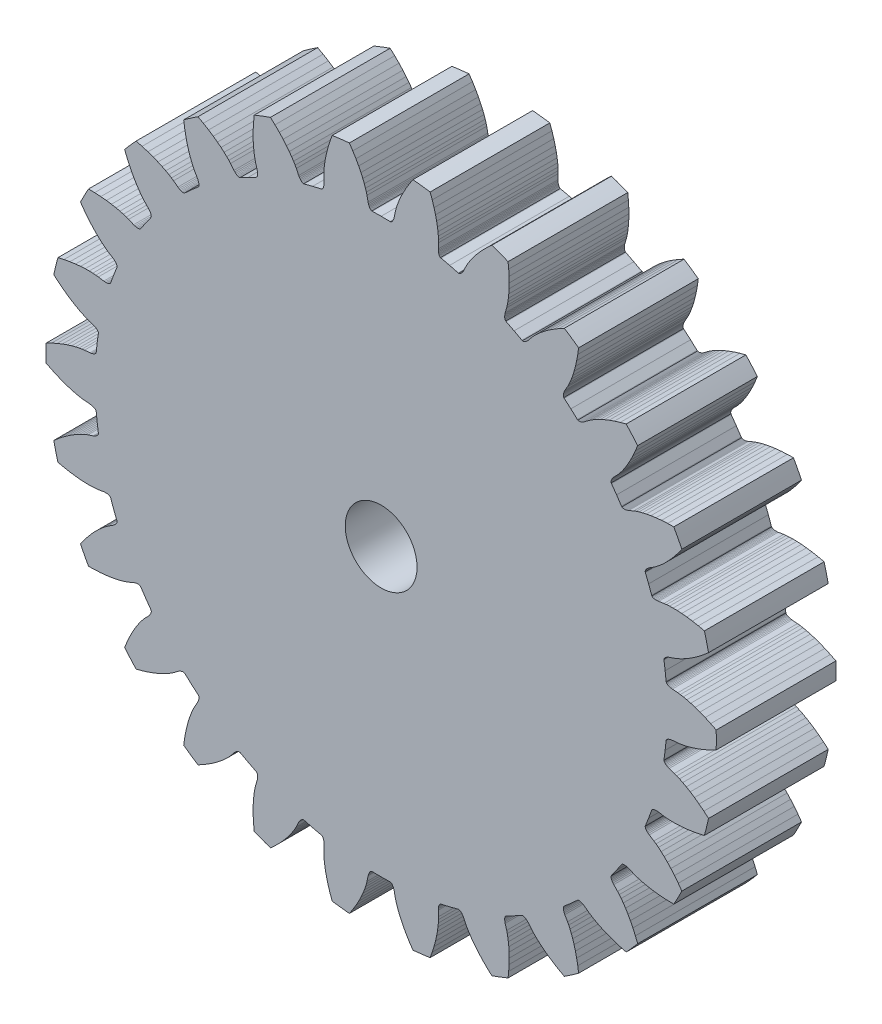
SolidWorks part; units mm, degrees
ref_plane "Front Plane" through (0, 0, 0) normal (0, 0, 1) x (1, 0, 0)
ref_plane "Top Plane" through (0, 0, 0) normal (0, 1, 0) x (1, 0, 0)
ref_plane "Right Plane" through (0, 0, 0) normal (1, 0, 0) x (0, 0, -1)
sketch "Model" plane through (0, 0, 0) normal (0, 0, 1) x (1, 0, 0)
  line L0 (13.4794, 2.8306) -> (13.2793, 2.6732)
  line L1 (13.2793, 2.6732) -> (13.0886, 2.5357)
  line L2 (13.0886, 2.5357) -> (12.9106, 2.4184)
  line L3 (12.9106, 2.4184) -> (12.7455, 2.3192)
  line L4 (12.7455, 2.3192) -> (12.5973, 2.2385)
  line L5 (12.5973, 2.2385) -> (12.4633, 2.1725)
  line L6 (12.4633, 2.1725) -> (12.3474, 2.1214)
  line L7 (12.3474, 2.1214) -> (12.2485, 2.0827)
  line L8 (12.2485, 2.0827) -> (12.0308, 2.0106)
  line L9 (12.0308, 2.0106) -> (11.9819, 1.9899)
  line L10 (11.9819, 1.9899) -> (11.9391, 1.9681)
  line L11 (11.9391, 1.9681) -> (11.9025, 1.9455)
  line L12 (11.9025, 1.9455) -> (11.8721, 1.9224)
  line L13 (11.8721, 1.9224) -> (11.8478, 1.899)
  line L14 (11.8478, 1.899) -> (11.8298, 1.8755)
  line L15 (11.8298, 1.8755) -> (11.8179, 1.8522)
  line L16 (11.8179, 1.8522) -> (11.8122, 1.8294)
  line L17 (11.8122, 1.8294) -> (11.8126, 1.8072)
  line L18 (11.8126, 1.8072) -> (11.8629, 1.4404)
  line L19 (11.8629, 1.4404) -> (11.9018, 1.0722)
  line L20 (11.9018, 1.0722) -> (11.9067, 1.0506)
  line L21 (11.9067, 1.0506) -> (11.9178, 1.0298)
  line L22 (11.9178, 1.0298) -> (11.9349, 1.0101)
  line L23 (11.9349, 1.0101) -> (11.958, 0.9916)
  line L24 (11.958, 0.9916) -> (11.9871, 0.9747)
  line L25 (11.9871, 0.9747) -> (12.0222, 0.9595)
  line L26 (12.0222, 0.9595) -> (12.0632, 0.9463)
  line L27 (12.0632, 0.9463) -> (12.1099, 0.9354)
  line L28 (12.1099, 0.9354) -> (12.1623, 0.927)
  line L29 (12.1623, 0.927) -> (12.391, 0.9091)
  line L30 (12.391, 0.9091) -> (12.4963, 0.8951)
  line L31 (12.4963, 0.8951) -> (12.6211, 0.8732)
  line L32 (12.6211, 0.8732) -> (12.7669, 0.8413)
  line L33 (12.7669, 0.8413) -> (12.9302, 0.7984)
  line L34 (12.9302, 0.7984) -> (13.1142, 0.7416)
  line L35 (13.1142, 0.7416) -> (13.3151, 0.6703)
  line L36 (13.3151, 0.6703) -> (13.5332, 0.5824)
  line L37 (13.5332, 0.5824) -> (13.7651, 0.4774)
  line L38 (13.7651, 0.4774) -> (13.9953, 0.3618)
  line L39 (13.9953, -0.3618) -> (13.7651, -0.4774)
  line L40 (13.7651, -0.4774) -> (13.5332, -0.5824)
  line L41 (13.5332, -0.5824) -> (13.3151, -0.6703)
  line L42 (13.3151, -0.6703) -> (13.1142, -0.7416)
  line L43 (13.1142, -0.7416) -> (12.9302, -0.7984)
  line L44 (12.9302, -0.7984) -> (12.7669, -0.8413)
  line L45 (12.7669, -0.8413) -> (12.6211, -0.8732)
  line L46 (12.6211, -0.8732) -> (12.4963, -0.8951)
  line L47 (12.4963, -0.8951) -> (12.391, -0.9091)
  line L48 (12.391, -0.9091) -> (12.1623, -0.927)
  line L49 (12.1623, -0.927) -> (12.1099, -0.9354)
  line L50 (12.1099, -0.9354) -> (12.0632, -0.9463)
  line L51 (12.0632, -0.9463) -> (12.0222, -0.9595)
  line L52 (12.0222, -0.9595) -> (11.9871, -0.9747)
  line L53 (11.9871, -0.9747) -> (11.958, -0.9916)
  line L54 (11.958, -0.9916) -> (11.9349, -1.0101)
  line L55 (11.9349, -1.0101) -> (11.9178, -1.0298)
  line L56 (11.9178, -1.0298) -> (11.9067, -1.0506)
  line L57 (11.9067, -1.0506) -> (11.9018, -1.0722)
  line L58 (11.9018, -1.0722) -> (11.8629, -1.4404)
  line L59 (11.8629, -1.4404) -> (11.8126, -1.8072)
  line L60 (11.8126, -1.8072) -> (11.8122, -1.8294)
  line L61 (11.8122, -1.8294) -> (11.8179, -1.8522)
  line L62 (11.8179, -1.8522) -> (11.8298, -1.8755)
  line L63 (11.8298, -1.8755) -> (11.8478, -1.899)
  line L64 (11.8478, -1.899) -> (11.8721, -1.9224)
  line L65 (11.8721, -1.9224) -> (11.9025, -1.9455)
  line L66 (11.9025, -1.9455) -> (11.9391, -1.9681)
  line L67 (11.9391, -1.9681) -> (11.9819, -1.9899)
  line L68 (11.9819, -1.9899) -> (12.0308, -2.0106)
  line L69 (12.0308, -2.0106) -> (12.2485, -2.0827)
  line L70 (12.2485, -2.0827) -> (12.3474, -2.1214)
  line L71 (12.3474, -2.1214) -> (12.4633, -2.1725)
  line L72 (12.4633, -2.1725) -> (12.5973, -2.2385)
  line L73 (12.5973, -2.2385) -> (12.7455, -2.3192)
  line L74 (12.7455, -2.3192) -> (12.9106, -2.4184)
  line L75 (12.9106, -2.4184) -> (13.0886, -2.5357)
  line L76 (13.0886, -2.5357) -> (13.2793, -2.6732)
  line L77 (13.2793, -2.6732) -> (13.4794, -2.8306)
  line L78 (13.4794, -2.8306) -> (13.6752, -2.9981)
  line L79 (13.5021, -3.7006) -> (13.2509, -3.7578)
  line L80 (13.2509, -3.7578) -> (13.0005, -3.8042)
  line L81 (13.0005, -3.8042) -> (12.7678, -3.8373)
  line L82 (12.7678, -3.8373) -> (12.5557, -3.8585)
  line L83 (12.5557, -3.8585) -> (12.3634, -3.8696)
  line L84 (12.3634, -3.8696) -> (12.1946, -3.8722)
  line L85 (12.1946, -3.8722) -> (12.0453, -3.8683)
  line L86 (12.0453, -3.8683) -> (11.919, -3.8597)
  line L87 (11.919, -3.8597) -> (11.8134, -3.848)
  line L88 (11.8134, -3.848) -> (11.5871, -3.8107)
  line L89 (11.5871, -3.8107) -> (11.5341, -3.8063)
  line L90 (11.5341, -3.8063) -> (11.4862, -3.8057)
  line L91 (11.4862, -3.8057) -> (11.4433, -3.8087)
  line L92 (11.4433, -3.8087) -> (11.4056, -3.815)
  line L93 (11.4056, -3.815) -> (11.3732, -3.8245)
  line L94 (11.3732, -3.8245) -> (11.3463, -3.8369)
  line L95 (11.3463, -3.8369) -> (11.325, -3.852)
  line L96 (11.325, -3.852) -> (11.3093, -3.8696)
  line L97 (11.3093, -3.8696) -> (11.2994, -3.8894)
  line L98 (11.2994, -3.8894) -> (11.1734, -4.2375)
  line L99 (11.1734, -4.2375) -> (11.0368, -4.5816)
  line L100 (11.0368, -4.5816) -> (11.0311, -4.603)
  line L101 (11.0311, -4.603) -> (11.0312, -4.6266)
  line L102 (11.0312, -4.6266) -> (11.0372, -4.652)
  line L103 (11.0372, -4.652) -> (11.0491, -4.6791)
  line L104 (11.0491, -4.6791) -> (11.067, -4.7077)
  line L105 (11.067, -4.7077) -> (11.091, -4.7374)
  line L106 (11.091, -4.7374) -> (11.1212, -4.7681)
  line L107 (11.1212, -4.7681) -> (11.1575, -4.7995)
  line L108 (11.1575, -4.7995) -> (11.2, -4.8313)
  line L109 (11.2, -4.8313) -> (11.3942, -4.9534)
  line L110 (11.3942, -4.9534) -> (11.4809, -5.0147)
  line L111 (11.4809, -5.0147) -> (11.5812, -5.0921)
  line L112 (11.5812, -5.0921) -> (11.6955, -5.1881)
  line L113 (11.6955, -5.1881) -> (11.8201, -5.302)
  line L114 (11.8201, -5.302) -> (11.9567, -5.4378)
  line L115 (11.9567, -5.4378) -> (12.1014, -5.5943)
  line L116 (12.1014, -5.5943) -> (12.2537, -5.7735)
  line L117 (12.2537, -5.7735) -> (12.4103, -5.9742)
  line L118 (12.4103, -5.9742) -> (12.5604, -6.1836)
  line L119 (12.2241, -6.8243) -> (11.9665, -6.8197)
  line L120 (11.9665, -6.8197) -> (11.7124, -6.8049)
  line L121 (11.7124, -6.8049) -> (11.4784, -6.7813)
  line L122 (11.4784, -6.7813) -> (11.2674, -6.7511)
  line L123 (11.2674, -6.7511) -> (11.0781, -6.7159)
  line L124 (11.0781, -6.7159) -> (10.9136, -6.678)
  line L125 (10.9136, -6.678) -> (10.7696, -6.6385)
  line L126 (10.7696, -6.6385) -> (10.6489, -6.5999)
  line L127 (10.6489, -6.5999) -> (10.5492, -6.5634)
  line L128 (10.5492, -6.5634) -> (10.3384, -6.4729)
  line L129 (10.3384, -6.4729) -> (10.2881, -6.456)
  line L130 (10.2881, -6.456) -> (10.2416, -6.444)
  line L131 (10.2416, -6.444) -> (10.1993, -6.4366)
  line L132 (10.1993, -6.4366) -> (10.1611, -6.4337)
  line L133 (10.1611, -6.4337) -> (10.1275, -6.4352)
  line L134 (10.1275, -6.4352) -> (10.0984, -6.4408)
  line L135 (10.0984, -6.4408) -> (10.0741, -6.4503)
  line L136 (10.0741, -6.4503) -> (10.0546, -6.4636)
  line L137 (10.0546, -6.4636) -> (10.0402, -6.4805)
  line L138 (10.0402, -6.4805) -> (9.8347, -6.7884)
  line L139 (9.8347, -6.7884) -> (9.6197, -7.0898)
  line L140 (9.6197, -7.0898) -> (9.609, -7.1092)
  line L141 (9.609, -7.1092) -> (9.6035, -7.1321)
  line L142 (9.6035, -7.1321) -> (9.6032, -7.1582)
  line L143 (9.6032, -7.1582) -> (9.6083, -7.1874)
  line L144 (9.6083, -7.1874) -> (9.6188, -7.2194)
  line L145 (9.6188, -7.2194) -> (9.635, -7.254)
  line L146 (9.635, -7.254) -> (9.6569, -7.291)
  line L147 (9.6569, -7.291) -> (9.6847, -7.3302)
  line L148 (9.6847, -7.3302) -> (9.7184, -7.3713)
  line L149 (9.7184, -7.3713) -> (9.8777, -7.5363)
  line L150 (9.8777, -7.5363) -> (9.9472, -7.6166)
  line L151 (9.9472, -7.6166) -> (10.0261, -7.7157)
  line L152 (10.0261, -7.7157) -> (10.1141, -7.8363)
  line L153 (10.1141, -7.8363) -> (10.2078, -7.9767)
  line L154 (10.2078, -7.9767) -> (10.3079, -8.1412)
  line L155 (10.3079, -8.1412) -> (10.411, -8.3278)
  line L156 (10.411, -8.3278) -> (10.5159, -8.5382)
  line L157 (10.5159, -8.5382) -> (10.6199, -8.7706)
  line L158 (10.6199, -8.7706) -> (10.7155, -9.0098)
  line L159 (10.2357, -9.5514) -> (9.9867, -9.4853)
  line L160 (9.9867, -9.4853) -> (9.7435, -9.4101)
  line L161 (9.7435, -9.4101) -> (9.522, -9.3312)
  line L162 (9.522, -9.3312) -> (9.3244, -9.2514)
  line L163 (9.3244, -9.2514) -> (9.149, -9.1719)
  line L164 (9.149, -9.1719) -> (8.9983, -9.0958)
  line L165 (8.9983, -9.0958) -> (8.8679, -9.0229)
  line L166 (8.8679, -9.0229) -> (8.76, -8.9566)
  line L167 (8.76, -8.9566) -> (8.672, -8.8972)
  line L168 (8.672, -8.8972) -> (8.4889, -8.759)
  line L169 (8.4889, -8.759) -> (8.4441, -8.7305)
  line L170 (8.4441, -8.7305) -> (8.4019, -8.7077)
  line L171 (8.4019, -8.7077) -> (8.3625, -8.6904)
  line L172 (8.3625, -8.6904) -> (8.3262, -8.6785)
  line L173 (8.3262, -8.6785) -> (8.2931, -8.6719)
  line L174 (8.2931, -8.6719) -> (8.2636, -8.6703)
  line L175 (8.2636, -8.6703) -> (8.2377, -8.6738)
  line L176 (8.2377, -8.6738) -> (8.2156, -8.682)
  line L177 (8.2156, -8.682) -> (8.1976, -8.6949)
  line L178 (8.1976, -8.6949) -> (7.9243, -8.9447)
  line L179 (7.9243, -8.9447) -> (7.6434, -9.1859)
  line L180 (7.6434, -9.1859) -> (7.6284, -9.2022)
  line L181 (7.6284, -9.2022) -> (7.6176, -9.2231)
  line L182 (7.6176, -9.2231) -> (7.6111, -9.2484)
  line L183 (7.6111, -9.2484) -> (7.609, -9.278)
  line L184 (7.609, -9.278) -> (7.6116, -9.3116)
  line L185 (7.6116, -9.3116) -> (7.619, -9.349)
  line L186 (7.619, -9.349) -> (7.6315, -9.3902)
  line L187 (7.6315, -9.3902) -> (7.649, -9.4349)
  line L188 (7.649, -9.4349) -> (7.6719, -9.4828)
  line L189 (7.6719, -9.4828) -> (7.7871, -9.6812)
  line L190 (7.7871, -9.6812) -> (7.8354, -9.7758)
  line L191 (7.8354, -9.7758) -> (7.8883, -9.8909)
  line L192 (7.8883, -9.8909) -> (7.9448, -10.0291)
  line L193 (7.9448, -10.0291) -> (8.0022, -10.1878)
  line L194 (8.0022, -10.1878) -> (8.06, -10.3715)
  line L195 (8.06, -10.3715) -> (8.1155, -10.5773)
  line L196 (8.1155, -10.5773) -> (8.167, -10.8067)
  line L197 (8.167, -10.8067) -> (8.2124, -11.0572)
  line L198 (8.2124, -11.0572) -> (8.248, -11.3124)
  line L199 (7.6525, -11.7234) -> (7.4265, -11.5997)
  line L200 (7.4265, -11.5997) -> (7.2084, -11.4684)
  line L201 (7.2084, -11.4684) -> (7.0122, -11.3389)
  line L202 (7.0122, -11.3389) -> (6.8394, -11.2141)
  line L203 (6.8394, -11.2141) -> (6.6881, -11.0948)
  line L204 (6.6881, -11.0948) -> (6.5601, -10.9849)
  line L205 (6.5601, -10.9849) -> (6.4509, -10.883)
  line L206 (6.4509, -10.883) -> (6.362, -10.7928)
  line L207 (6.362, -10.7928) -> (6.2907, -10.714)
  line L208 (6.2907, -10.714) -> (6.1461, -10.536)
  line L209 (6.1461, -10.536) -> (6.1094, -10.4976)
  line L210 (6.1094, -10.4976) -> (6.0738, -10.4654)
  line L211 (6.0738, -10.4654) -> (6.0398, -10.4391)
  line L212 (6.0398, -10.4391) -> (6.0073, -10.4189)
  line L213 (6.0073, -10.4189) -> (5.9769, -10.4045)
  line L214 (5.9769, -10.4045) -> (5.9485, -10.396)
  line L215 (5.9485, -10.396) -> (5.9225, -10.3931)
  line L216 (5.9225, -10.3931) -> (5.8991, -10.3959)
  line L217 (5.8991, -10.3959) -> (5.8786, -10.4041)
  line L218 (5.8786, -10.4041) -> (5.5534, -10.5812)
  line L219 (5.5534, -10.5812) -> (5.223, -10.7482)
  line L220 (5.223, -10.7482) -> (5.2045, -10.7604)
  line L221 (5.2045, -10.7604) -> (5.189, -10.7781)
  line L222 (5.189, -10.7781) -> (5.1766, -10.8011)
  line L223 (5.1766, -10.8011) -> (5.1675, -10.8293)
  line L224 (5.1675, -10.8293) -> (5.162, -10.8626)
  line L225 (5.162, -10.8626) -> (5.1603, -10.9007)
  line L226 (5.1603, -10.9007) -> (5.1625, -10.9437)
  line L227 (5.1625, -10.9437) -> (5.1689, -10.9912)
  line L228 (5.1689, -10.9912) -> (5.1796, -11.0433)
  line L229 (5.1796, -11.0433) -> (5.2439, -11.2634)
  line L230 (5.2439, -11.2634) -> (5.2682, -11.3668)
  line L231 (5.2682, -11.3668) -> (5.292, -11.4912)
  line L232 (5.292, -11.4912) -> (5.3139, -11.639)
  line L233 (5.3139, -11.639) -> (5.3316, -11.8068)
  line L234 (5.3316, -11.8068) -> (5.3438, -11.999)
  line L235 (5.3438, -11.999) -> (5.3483, -12.2121)
  line L236 (5.3483, -12.2121) -> (5.3435, -12.4472)
  line L237 (5.3435, -12.4472) -> (5.3276, -12.7013)
  line L238 (5.3276, -12.7013) -> (5.3011, -12.9576)
  line L239 (4.6246, -13.2141) -> (4.4348, -13.0399)
  line L240 (4.4348, -13.0399) -> (4.2544, -12.8603)
  line L241 (4.2544, -12.8603) -> (4.0949, -12.6875)
  line L242 (4.0949, -12.6875) -> (3.957, -12.525)
  line L243 (3.957, -12.525) -> (3.8386, -12.373)
  line L244 (3.8386, -12.373) -> (3.7406, -12.2356)
  line L245 (3.7406, -12.2356) -> (3.659, -12.1106)
  line L246 (3.659, -12.1106) -> (3.5943, -12.0017)
  line L247 (3.5943, -12.0017) -> (3.5439, -11.9082)
  line L248 (3.5439, -11.9082) -> (3.4461, -11.7007)
  line L249 (3.4461, -11.7007) -> (3.4196, -11.6546)
  line L250 (3.4196, -11.6546) -> (3.3928, -11.6148)
  line L251 (3.3928, -11.6148) -> (3.366, -11.5812)
  line L252 (3.366, -11.5812) -> (3.3394, -11.5538)
  line L253 (3.3394, -11.5538) -> (3.3132, -11.5326)
  line L254 (3.3132, -11.5326) -> (3.2877, -11.5175)
  line L255 (3.2877, -11.5175) -> (3.2632, -11.5085)
  line L256 (3.2632, -11.5085) -> (3.2398, -11.5055)
  line L257 (3.2398, -11.5055) -> (3.2179, -11.5086)
  line L258 (3.2179, -11.5086) -> (2.8598, -11.6028)
  line L259 (2.8598, -11.6028) -> (2.499, -11.6858)
  line L260 (2.499, -11.6858) -> (2.4782, -11.6933)
  line L261 (2.4782, -11.6933) -> (2.4589, -11.7067)
  line L262 (2.4589, -11.7067) -> (2.4413, -11.7261)
  line L263 (2.4413, -11.7261) -> (2.4257, -11.7513)
  line L264 (2.4257, -11.7513) -> (2.4124, -11.7823)
  line L265 (2.4124, -11.7823) -> (2.4016, -11.8189)
  line L266 (2.4016, -11.8189) -> (2.3935, -11.8611)
  line L267 (2.3935, -11.8611) -> (2.3883, -11.9088)
  line L268 (2.3883, -11.9088) -> (2.3862, -11.9619)
  line L269 (2.3862, -11.9619) -> (2.396, -12.1911)
  line L270 (2.396, -12.1911) -> (2.3949, -12.2973)
  line L271 (2.3949, -12.2973) -> (2.3882, -12.4238)
  line L272 (2.3882, -12.4238) -> (2.3741, -12.5724)
  line L273 (2.3741, -12.5724) -> (2.3511, -12.7397)
  line L274 (2.3511, -12.7397) -> (2.3169, -12.9292)
  line L275 (2.3169, -12.9292) -> (2.2704, -13.1372)
  line L276 (2.2704, -13.1372) -> (2.2094, -13.3643)
  line L277 (2.2094, -13.3643) -> (2.1332, -13.6072)
  line L278 (2.1332, -13.6072) -> (2.0461, -13.8497)
  line L279 (1.3278, -13.9369) -> (1.1852, -13.7223)
  line L280 (1.1852, -13.7223) -> (1.0531, -13.5047)
  line L281 (1.0531, -13.5047) -> (0.9396, -13.2988)
  line L282 (0.9396, -13.2988) -> (0.8446, -13.108)
  line L283 (0.8446, -13.108) -> (0.766, -12.9321)
  line L284 (0.766, -12.9321) -> (0.7037, -12.7753)
  line L285 (0.7037, -12.7753) -> (0.6544, -12.6343)
  line L286 (0.6544, -12.6343) -> (0.6177, -12.5131)
  line L287 (0.6177, -12.5131) -> (0.5911, -12.4102)
  line L288 (0.5911, -12.4102) -> (0.5458, -12.1854)
  line L289 (0.5458, -12.1854) -> (0.5311, -12.1343)
  line L290 (0.5311, -12.1343) -> (0.5146, -12.0893)
  line L291 (0.5146, -12.0893) -> (0.4966, -12.0502)
  line L292 (0.4966, -12.0502) -> (0.4773, -12.0172)
  line L293 (0.4773, -12.0172) -> (0.457, -11.9904)
  line L294 (0.457, -11.9904) -> (0.4359, -11.9696)
  line L295 (0.4359, -11.9696) -> (0.4142, -11.955)
  line L296 (0.4142, -11.955) -> (0.3922, -11.9466)
  line L297 (0.3922, -11.9466) -> (0.3702, -11.9443)
  line L298 (0.3702, -11.9443) -> (0, -11.95)
  line L299 (0, -11.95) -> (-0.3702, -11.9443)
  line L300 (-0.3702, -11.9443) -> (-0.3922, -11.9466)
  line L301 (-0.3922, -11.9466) -> (-0.4142, -11.955)
  line L302 (-0.4142, -11.955) -> (-0.4359, -11.9696)
  line L303 (-0.4359, -11.9696) -> (-0.457, -11.9904)
  line L304 (-0.457, -11.9904) -> (-0.4773, -12.0172)
  line L305 (-0.4773, -12.0172) -> (-0.4966, -12.0502)
  line L306 (-0.4966, -12.0502) -> (-0.5146, -12.0893)
  line L307 (-0.5146, -12.0893) -> (-0.5311, -12.1343)
  line L308 (-0.5311, -12.1343) -> (-0.5458, -12.1854)
  line L309 (-0.5458, -12.1854) -> (-0.5911, -12.4102)
  line L310 (-0.5911, -12.4102) -> (-0.6177, -12.5131)
  line L311 (-0.6177, -12.5131) -> (-0.6544, -12.6343)
  line L312 (-0.6544, -12.6343) -> (-0.7037, -12.7753)
  line L313 (-0.7037, -12.7753) -> (-0.766, -12.9321)
  line L314 (-0.766, -12.9321) -> (-0.8446, -13.108)
  line L315 (-0.8446, -13.108) -> (-0.9396, -13.2988)
  line L316 (-0.9396, -13.2988) -> (-1.0531, -13.5047)
  line L317 (-1.0531, -13.5047) -> (-1.1852, -13.7223)
  line L318 (-1.1852, -13.7223) -> (-1.3278, -13.9369)
  line L319 (-2.0461, -13.8497) -> (-2.1332, -13.6072)
  line L320 (-2.1332, -13.6072) -> (-2.2094, -13.3643)
  line L321 (-2.2094, -13.3643) -> (-2.2704, -13.1372)
  line L322 (-2.2704, -13.1372) -> (-2.3169, -12.9292)
  line L323 (-2.3169, -12.9292) -> (-2.3511, -12.7397)
  line L324 (-2.3511, -12.7397) -> (-2.3741, -12.5724)
  line L325 (-2.3741, -12.5724) -> (-2.3882, -12.4238)
  line L326 (-2.3882, -12.4238) -> (-2.3949, -12.2973)
  line L327 (-2.3949, -12.2973) -> (-2.396, -12.1911)
  line L328 (-2.396, -12.1911) -> (-2.3862, -11.9619)
  line L329 (-2.3862, -11.9619) -> (-2.3883, -11.9088)
  line L330 (-2.3883, -11.9088) -> (-2.3935, -11.8611)
  line L331 (-2.3935, -11.8611) -> (-2.4016, -11.8189)
  line L332 (-2.4016, -11.8189) -> (-2.4124, -11.7823)
  line L333 (-2.4124, -11.7823) -> (-2.4257, -11.7513)
  line L334 (-2.4257, -11.7513) -> (-2.4413, -11.7261)
  line L335 (-2.4413, -11.7261) -> (-2.4589, -11.7067)
  line L336 (-2.4589, -11.7067) -> (-2.4782, -11.6933)
  line L337 (-2.4782, -11.6933) -> (-2.499, -11.6858)
  line L338 (-2.499, -11.6858) -> (-2.8598, -11.6028)
  line L339 (-2.8598, -11.6028) -> (-3.2179, -11.5086)
  line L340 (-3.2179, -11.5086) -> (-3.2398, -11.5055)
  line L341 (-3.2398, -11.5055) -> (-3.2632, -11.5085)
  line L342 (-3.2632, -11.5085) -> (-3.2877, -11.5175)
  line L343 (-3.2877, -11.5175) -> (-3.3132, -11.5326)
  line L344 (-3.3132, -11.5326) -> (-3.3394, -11.5538)
  line L345 (-3.3394, -11.5538) -> (-3.366, -11.5812)
  line L346 (-3.366, -11.5812) -> (-3.3928, -11.6148)
  line L347 (-3.3928, -11.6148) -> (-3.4196, -11.6546)
  line L348 (-3.4196, -11.6546) -> (-3.4461, -11.7007)
  line L349 (-3.4461, -11.7007) -> (-3.5439, -11.9082)
  line L350 (-3.5439, -11.9082) -> (-3.5943, -12.0017)
  line L351 (-3.5943, -12.0017) -> (-3.659, -12.1106)
  line L352 (-3.659, -12.1106) -> (-3.7406, -12.2356)
  line L353 (-3.7406, -12.2356) -> (-3.8386, -12.373)
  line L354 (-3.8386, -12.373) -> (-3.957, -12.525)
  line L355 (-3.957, -12.525) -> (-4.0949, -12.6875)
  line L356 (-4.0949, -12.6875) -> (-4.2544, -12.8603)
  line L357 (-4.2544, -12.8603) -> (-4.4348, -13.0399)
  line L358 (-4.4348, -13.0399) -> (-4.6246, -13.2141)
  line L359 (-5.3011, -12.9576) -> (-5.3276, -12.7013)
  line L360 (-5.3276, -12.7013) -> (-5.3435, -12.4472)
  line L361 (-5.3435, -12.4472) -> (-5.3483, -12.2121)
  line L362 (-5.3483, -12.2121) -> (-5.3438, -11.999)
  line L363 (-5.3438, -11.999) -> (-5.3316, -11.8068)
  line L364 (-5.3316, -11.8068) -> (-5.3139, -11.639)
  line L365 (-5.3139, -11.639) -> (-5.292, -11.4912)
  line L366 (-5.292, -11.4912) -> (-5.2682, -11.3668)
  line L367 (-5.2682, -11.3668) -> (-5.2439, -11.2634)
  line L368 (-5.2439, -11.2634) -> (-5.1796, -11.0433)
  line L369 (-5.1796, -11.0433) -> (-5.1689, -10.9912)
  line L370 (-5.1689, -10.9912) -> (-5.1625, -10.9437)
  line L371 (-5.1625, -10.9437) -> (-5.1603, -10.9007)
  line L372 (-5.1603, -10.9007) -> (-5.162, -10.8626)
  line L373 (-5.162, -10.8626) -> (-5.1675, -10.8293)
  line L374 (-5.1675, -10.8293) -> (-5.1766, -10.8011)
  line L375 (-5.1766, -10.8011) -> (-5.189, -10.7781)
  line L376 (-5.189, -10.7781) -> (-5.2045, -10.7604)
  line L377 (-5.2045, -10.7604) -> (-5.223, -10.7482)
  line L378 (-5.223, -10.7482) -> (-5.5534, -10.5812)
  line L379 (-5.5534, -10.5812) -> (-5.8786, -10.4041)
  line L380 (-5.8786, -10.4041) -> (-5.8991, -10.3959)
  line L381 (-5.8991, -10.3959) -> (-5.9225, -10.3931)
  line L382 (-5.9225, -10.3931) -> (-5.9485, -10.396)
  line L383 (-5.9485, -10.396) -> (-5.9769, -10.4045)
  line L384 (-5.9769, -10.4045) -> (-6.0073, -10.4189)
  line L385 (-6.0073, -10.4189) -> (-6.0398, -10.4391)
  line L386 (-6.0398, -10.4391) -> (-6.0738, -10.4654)
  line L387 (-6.0738, -10.4654) -> (-6.1094, -10.4976)
  line L388 (-6.1094, -10.4976) -> (-6.1461, -10.536)
  line L389 (-6.1461, -10.536) -> (-6.2907, -10.714)
  line L390 (-6.2907, -10.714) -> (-6.362, -10.7928)
  line L391 (-6.362, -10.7928) -> (-6.4509, -10.883)
  line L392 (-6.4509, -10.883) -> (-6.5601, -10.9849)
  line L393 (-6.5601, -10.9849) -> (-6.6881, -11.0948)
  line L394 (-6.6881, -11.0948) -> (-6.8394, -11.2141)
  line L395 (-6.8394, -11.2141) -> (-7.0122, -11.3389)
  line L396 (-7.0122, -11.3389) -> (-7.2084, -11.4684)
  line L397 (-7.2084, -11.4684) -> (-7.4265, -11.5997)
  line L398 (-7.4265, -11.5997) -> (-7.6525, -11.7234)
  line L399 (-8.248, -11.3124) -> (-8.2124, -11.0572)
  line L400 (-8.2124, -11.0572) -> (-8.167, -10.8067)
  line L401 (-8.167, -10.8067) -> (-8.1155, -10.5773)
  line L402 (-8.1155, -10.5773) -> (-8.06, -10.3715)
  line L403 (-8.06, -10.3715) -> (-8.0022, -10.1878)
  line L404 (-8.0022, -10.1878) -> (-7.9448, -10.0291)
  line L405 (-7.9448, -10.0291) -> (-7.8883, -9.8909)
  line L406 (-7.8883, -9.8909) -> (-7.8354, -9.7758)
  line L407 (-7.8354, -9.7758) -> (-7.7871, -9.6812)
  line L408 (-7.7871, -9.6812) -> (-7.6719, -9.4828)
  line L409 (-7.6719, -9.4828) -> (-7.649, -9.4349)
  line L410 (-7.649, -9.4349) -> (-7.6315, -9.3902)
  line L411 (-7.6315, -9.3902) -> (-7.619, -9.349)
  line L412 (-7.619, -9.349) -> (-7.6116, -9.3116)
  line L413 (-7.6116, -9.3116) -> (-7.609, -9.278)
  line L414 (-7.609, -9.278) -> (-7.6111, -9.2484)
  line L415 (-7.6111, -9.2484) -> (-7.6176, -9.2231)
  line L416 (-7.6176, -9.2231) -> (-7.6284, -9.2022)
  line L417 (-7.6284, -9.2022) -> (-7.6434, -9.1859)
  line L418 (-7.6434, -9.1859) -> (-7.9243, -8.9447)
  line L419 (-7.9243, -8.9447) -> (-8.1976, -8.6949)
  line L420 (-8.1976, -8.6949) -> (-8.2156, -8.682)
  line L421 (-8.2156, -8.682) -> (-8.2377, -8.6738)
  line L422 (-8.2377, -8.6738) -> (-8.2636, -8.6703)
  line L423 (-8.2636, -8.6703) -> (-8.2931, -8.6719)
  line L424 (-8.2931, -8.6719) -> (-8.3262, -8.6785)
  line L425 (-8.3262, -8.6785) -> (-8.3625, -8.6904)
  line L426 (-8.3625, -8.6904) -> (-8.4019, -8.7077)
  line L427 (-8.4019, -8.7077) -> (-8.4441, -8.7305)
  line L428 (-8.4441, -8.7305) -> (-8.4889, -8.759)
  line L429 (-8.4889, -8.759) -> (-8.672, -8.8972)
  line L430 (-8.672, -8.8972) -> (-8.76, -8.9566)
  line L431 (-8.76, -8.9566) -> (-8.8679, -9.0229)
  line L432 (-8.8679, -9.0229) -> (-8.9983, -9.0958)
  line L433 (-8.9983, -9.0958) -> (-9.149, -9.1719)
  line L434 (-9.149, -9.1719) -> (-9.3244, -9.2514)
  line L435 (-9.3244, -9.2514) -> (-9.522, -9.3312)
  line L436 (-9.522, -9.3312) -> (-9.7435, -9.4101)
  line L437 (-9.7435, -9.4101) -> (-9.9867, -9.4853)
  line L438 (-9.9867, -9.4853) -> (-10.2358, -9.5514)
  line L439 (-10.7156, -9.0098) -> (-10.6199, -8.7706)
  line L440 (-10.6199, -8.7706) -> (-10.5159, -8.5382)
  line L441 (-10.5159, -8.5382) -> (-10.411, -8.3278)
  line L442 (-10.411, -8.3278) -> (-10.3079, -8.1412)
  line L443 (-10.3079, -8.1412) -> (-10.2078, -7.9767)
  line L444 (-10.2078, -7.9767) -> (-10.1141, -7.8363)
  line L445 (-10.1141, -7.8363) -> (-10.0261, -7.7157)
  line L446 (-10.0261, -7.7157) -> (-9.9472, -7.6166)
  line L447 (-9.9472, -7.6166) -> (-9.8777, -7.5363)
  line L448 (-9.8777, -7.5363) -> (-9.7184, -7.3713)
  line L449 (-9.7184, -7.3713) -> (-9.6847, -7.3302)
  line L450 (-9.6847, -7.3302) -> (-9.6569, -7.291)
  line L451 (-9.6569, -7.291) -> (-9.635, -7.254)
  line L452 (-9.635, -7.254) -> (-9.6188, -7.2194)
  line L453 (-9.6188, -7.2194) -> (-9.6083, -7.1874)
  line L454 (-9.6083, -7.1874) -> (-9.6032, -7.1582)
  line L455 (-9.6032, -7.1582) -> (-9.6035, -7.1321)
  line L456 (-9.6035, -7.1321) -> (-9.609, -7.1092)
  line L457 (-9.609, -7.1092) -> (-9.6197, -7.0898)
  line L458 (-9.6197, -7.0898) -> (-9.8347, -6.7884)
  line L459 (-9.8347, -6.7884) -> (-10.0402, -6.4805)
  line L460 (-10.0402, -6.4805) -> (-10.0546, -6.4636)
  line L461 (-10.0546, -6.4636) -> (-10.0741, -6.4503)
  line L462 (-10.0741, -6.4503) -> (-10.0984, -6.4408)
  line L463 (-10.0984, -6.4408) -> (-10.1275, -6.4352)
  line L464 (-10.1275, -6.4352) -> (-10.1611, -6.4337)
  line L465 (-10.1611, -6.4337) -> (-10.1993, -6.4366)
  line L466 (-10.1993, -6.4366) -> (-10.2416, -6.444)
  line L467 (-10.2416, -6.444) -> (-10.2881, -6.456)
  line L468 (-10.2881, -6.456) -> (-10.3384, -6.4729)
  line L469 (-10.3384, -6.4729) -> (-10.5492, -6.5634)
  line L470 (-10.5492, -6.5634) -> (-10.6489, -6.5999)
  line L471 (-10.6489, -6.5999) -> (-10.7696, -6.6385)
  line L472 (-10.7696, -6.6385) -> (-10.9136, -6.678)
  line L473 (-10.9136, -6.678) -> (-11.0781, -6.7159)
  line L474 (-11.0781, -6.7159) -> (-11.2674, -6.7511)
  line L475 (-11.2674, -6.7511) -> (-11.4784, -6.7813)
  line L476 (-11.4784, -6.7813) -> (-11.7124, -6.8049)
  line L477 (-11.7124, -6.8049) -> (-11.9665, -6.8197)
  line L478 (-11.9665, -6.8197) -> (-12.2241, -6.8243)
  line L479 (-12.5604, -6.1836) -> (-12.4103, -5.9742)
  line L480 (-12.4103, -5.9742) -> (-12.2537, -5.7735)
  line L481 (-12.2537, -5.7735) -> (-12.1014, -5.5943)
  line L482 (-12.1014, -5.5943) -> (-11.9567, -5.4378)
  line L483 (-11.9567, -5.4378) -> (-11.8201, -5.302)
  line L484 (-11.8201, -5.302) -> (-11.6955, -5.1881)
  line L485 (-11.6955, -5.1881) -> (-11.5812, -5.0921)
  line L486 (-11.5812, -5.0921) -> (-11.4809, -5.0147)
  line L487 (-11.4809, -5.0147) -> (-11.3942, -4.9534)
  line L488 (-11.3942, -4.9534) -> (-11.2, -4.8313)
  line L489 (-11.2, -4.8313) -> (-11.1575, -4.7995)
  line L490 (-11.1575, -4.7995) -> (-11.1212, -4.7681)
  line L491 (-11.1212, -4.7681) -> (-11.091, -4.7374)
  line L492 (-11.091, -4.7374) -> (-11.067, -4.7077)
  line L493 (-11.067, -4.7077) -> (-11.0491, -4.6791)
  line L494 (-11.0491, -4.6791) -> (-11.0372, -4.652)
  line L495 (-11.0372, -4.652) -> (-11.0312, -4.6266)
  line L496 (-11.0312, -4.6266) -> (-11.0311, -4.603)
  line L497 (-11.0311, -4.603) -> (-11.0368, -4.5816)
  line L498 (-11.0368, -4.5816) -> (-11.1734, -4.2375)
  line L499 (-11.1734, -4.2375) -> (-11.2994, -3.8894)
  line L500 (-11.2994, -3.8894) -> (-11.3093, -3.8696)
  line L501 (-11.3093, -3.8696) -> (-11.325, -3.852)
  line L502 (-11.325, -3.852) -> (-11.3463, -3.8369)
  line L503 (-11.3463, -3.8369) -> (-11.3732, -3.8245)
  line L504 (-11.3732, -3.8245) -> (-11.4056, -3.815)
  line L505 (-11.4056, -3.815) -> (-11.4433, -3.8087)
  line L506 (-11.4433, -3.8087) -> (-11.4862, -3.8057)
  line L507 (-11.4862, -3.8057) -> (-11.5341, -3.8063)
  line L508 (-11.5341, -3.8063) -> (-11.5871, -3.8107)
  line L509 (-11.5871, -3.8107) -> (-11.8134, -3.848)
  line L510 (-11.8134, -3.848) -> (-11.919, -3.8597)
  line L511 (-11.919, -3.8597) -> (-12.0453, -3.8683)
  line L512 (-12.0453, -3.8683) -> (-12.1946, -3.8722)
  line L513 (-12.1946, -3.8722) -> (-12.3634, -3.8696)
  line L514 (-12.3634, -3.8696) -> (-12.5557, -3.8585)
  line L515 (-12.5557, -3.8585) -> (-12.7678, -3.8373)
  line L516 (-12.7678, -3.8373) -> (-13.0005, -3.8042)
  line L517 (-13.0005, -3.8042) -> (-13.2509, -3.7578)
  line L518 (-13.2509, -3.7578) -> (-13.5021, -3.7005)
  line L519 (-13.6752, -2.9981) -> (-13.4794, -2.8306)
  line L520 (-13.4794, -2.8306) -> (-13.2793, -2.6732)
  line L521 (-13.2793, -2.6732) -> (-13.0886, -2.5357)
  line L522 (-13.0886, -2.5357) -> (-12.9106, -2.4184)
  line L523 (-12.9106, -2.4184) -> (-12.7455, -2.3192)
  line L524 (-12.7455, -2.3192) -> (-12.5973, -2.2385)
  line L525 (-12.5973, -2.2385) -> (-12.4633, -2.1725)
  line L526 (-12.4633, -2.1725) -> (-12.3474, -2.1214)
  line L527 (-12.3474, -2.1214) -> (-12.2485, -2.0827)
  line L528 (-12.2485, -2.0827) -> (-12.0308, -2.0106)
  line L529 (-12.0308, -2.0106) -> (-11.9819, -1.9899)
  line L530 (-11.9819, -1.9899) -> (-11.9391, -1.9681)
  line L531 (-11.9391, -1.9681) -> (-11.9025, -1.9455)
  line L532 (-11.9025, -1.9455) -> (-11.8721, -1.9224)
  line L533 (-11.8721, -1.9224) -> (-11.8478, -1.899)
  line L534 (-11.8478, -1.899) -> (-11.8298, -1.8755)
  line L535 (-11.8298, -1.8755) -> (-11.8179, -1.8522)
  line L536 (-11.8179, -1.8522) -> (-11.8122, -1.8294)
  line L537 (-11.8122, -1.8294) -> (-11.8126, -1.8072)
  line L538 (-11.8126, -1.8072) -> (-11.8629, -1.4404)
  line L539 (-11.8629, -1.4404) -> (-11.9018, -1.0722)
  line L540 (-11.9018, -1.0722) -> (-11.9067, -1.0506)
  line L541 (-11.9067, -1.0506) -> (-11.9178, -1.0298)
  line L542 (-11.9178, -1.0298) -> (-11.9349, -1.0101)
  line L543 (-11.9349, -1.0101) -> (-11.958, -0.9916)
  line L544 (-11.958, -0.9916) -> (-11.9871, -0.9747)
  line L545 (-11.9871, -0.9747) -> (-12.0222, -0.9595)
  line L546 (-12.0222, -0.9595) -> (-12.0632, -0.9463)
  line L547 (-12.0632, -0.9463) -> (-12.1099, -0.9354)
  line L548 (-12.1099, -0.9354) -> (-12.1623, -0.927)
  line L549 (-12.1623, -0.927) -> (-12.391, -0.9091)
  line L550 (-12.391, -0.9091) -> (-12.4963, -0.8951)
  line L551 (-12.4963, -0.8951) -> (-12.6211, -0.8732)
  line L552 (-12.6211, -0.8732) -> (-12.7669, -0.8413)
  line L553 (-12.7669, -0.8413) -> (-12.9302, -0.7984)
  line L554 (-12.9302, -0.7984) -> (-13.1142, -0.7416)
  line L555 (-13.1142, -0.7416) -> (-13.3151, -0.6703)
  line L556 (-13.3151, -0.6703) -> (-13.5332, -0.5824)
  line L557 (-13.5332, -0.5824) -> (-13.7651, -0.4774)
  line L558 (-13.7651, -0.4774) -> (-13.9953, -0.3618)
  line L559 (-13.9953, 0.3618) -> (-13.7651, 0.4774)
  line L560 (-13.7651, 0.4774) -> (-13.5332, 0.5824)
  line L561 (-13.5332, 0.5824) -> (-13.3151, 0.6703)
  line L562 (-13.3151, 0.6703) -> (-13.1142, 0.7416)
  line L563 (-13.1142, 0.7416) -> (-12.9302, 0.7984)
  line L564 (-12.9302, 0.7984) -> (-12.7669, 0.8413)
  line L565 (-12.7669, 0.8413) -> (-12.6211, 0.8732)
  line L566 (-12.6211, 0.8732) -> (-12.4963, 0.8951)
  line L567 (-12.4963, 0.8951) -> (-12.391, 0.9091)
  line L568 (-12.391, 0.9091) -> (-12.1623, 0.927)
  line L569 (-12.1623, 0.927) -> (-12.1099, 0.9354)
  line L570 (-12.1099, 0.9354) -> (-12.0632, 0.9463)
  line L571 (-12.0632, 0.9463) -> (-12.0222, 0.9595)
  line L572 (-12.0222, 0.9595) -> (-11.9871, 0.9747)
  line L573 (-11.9871, 0.9747) -> (-11.958, 0.9916)
  line L574 (-11.958, 0.9916) -> (-11.9349, 1.0101)
  line L575 (-11.9349, 1.0101) -> (-11.9178, 1.0298)
  line L576 (-11.9178, 1.0298) -> (-11.9067, 1.0506)
  line L577 (-11.9067, 1.0506) -> (-11.9018, 1.0722)
  line L578 (-11.9018, 1.0722) -> (-11.8629, 1.4404)
  line L579 (-11.8629, 1.4404) -> (-11.8126, 1.8072)
  line L580 (-11.8126, 1.8072) -> (-11.8122, 1.8294)
  line L581 (-11.8122, 1.8294) -> (-11.8179, 1.8522)
  line L582 (-11.8179, 1.8522) -> (-11.8298, 1.8755)
  line L583 (-11.8298, 1.8755) -> (-11.8478, 1.899)
  line L584 (-11.8478, 1.899) -> (-11.8721, 1.9224)
  line L585 (-11.8721, 1.9224) -> (-11.9025, 1.9455)
  line L586 (-11.9025, 1.9455) -> (-11.9391, 1.9681)
  line L587 (-11.9391, 1.9681) -> (-11.9819, 1.9899)
  line L588 (-11.9819, 1.9899) -> (-12.0308, 2.0106)
  line L589 (-12.0308, 2.0106) -> (-12.2485, 2.0827)
  line L590 (-12.2485, 2.0827) -> (-12.3474, 2.1214)
  line L591 (-12.3474, 2.1214) -> (-12.4633, 2.1725)
  line L592 (-12.4633, 2.1725) -> (-12.5973, 2.2385)
  line L593 (-12.5973, 2.2385) -> (-12.7455, 2.3192)
  line L594 (-12.7455, 2.3192) -> (-12.9106, 2.4184)
  line L595 (-12.9106, 2.4184) -> (-13.0886, 2.5357)
  line L596 (-13.0886, 2.5357) -> (-13.2793, 2.6732)
  line L597 (-13.2793, 2.6732) -> (-13.4794, 2.8306)
  line L598 (-13.4794, 2.8306) -> (-13.6752, 2.9981)
  line L599 (-13.5021, 3.7006) -> (-13.2509, 3.7578)
  line L600 (-13.2509, 3.7578) -> (-13.0005, 3.8042)
  line L601 (-13.0005, 3.8042) -> (-12.7678, 3.8373)
  line L602 (-12.7678, 3.8373) -> (-12.5557, 3.8585)
  line L603 (-12.5557, 3.8585) -> (-12.3634, 3.8696)
  line L604 (-12.3634, 3.8696) -> (-12.1946, 3.8722)
  line L605 (-12.1946, 3.8722) -> (-12.0453, 3.8683)
  line L606 (-12.0453, 3.8683) -> (-11.919, 3.8597)
  line L607 (-11.919, 3.8597) -> (-11.8134, 3.848)
  line L608 (-11.8134, 3.848) -> (-11.5871, 3.8107)
  line L609 (-11.5871, 3.8107) -> (-11.5341, 3.8063)
  line L610 (-11.5341, 3.8063) -> (-11.4862, 3.8057)
  line L611 (-11.4862, 3.8057) -> (-11.4433, 3.8087)
  line L612 (-11.4433, 3.8087) -> (-11.4056, 3.815)
  line L613 (-11.4056, 3.815) -> (-11.3732, 3.8245)
  line L614 (-11.3732, 3.8245) -> (-11.3463, 3.8369)
  line L615 (-11.3463, 3.8369) -> (-11.325, 3.852)
  line L616 (-11.325, 3.852) -> (-11.3093, 3.8696)
  line L617 (-11.3093, 3.8696) -> (-11.2994, 3.8894)
  line L618 (-11.2994, 3.8894) -> (-11.1734, 4.2375)
  line L619 (-11.1734, 4.2375) -> (-11.0368, 4.5816)
  line L620 (-11.0368, 4.5816) -> (-11.0311, 4.603)
  line L621 (-11.0311, 4.603) -> (-11.0312, 4.6266)
  line L622 (-11.0312, 4.6266) -> (-11.0372, 4.652)
  line L623 (-11.0372, 4.652) -> (-11.0491, 4.6791)
  line L624 (-11.0491, 4.6791) -> (-11.067, 4.7077)
  line L625 (-11.067, 4.7077) -> (-11.091, 4.7374)
  line L626 (-11.091, 4.7374) -> (-11.1212, 4.7681)
  line L627 (-11.1212, 4.7681) -> (-11.1575, 4.7995)
  line L628 (-11.1575, 4.7995) -> (-11.2, 4.8313)
  line L629 (-11.2, 4.8313) -> (-11.3942, 4.9534)
  line L630 (-11.3942, 4.9534) -> (-11.4809, 5.0147)
  line L631 (-11.4809, 5.0147) -> (-11.5812, 5.0921)
  line L632 (-11.5812, 5.0921) -> (-11.6955, 5.1881)
  line L633 (-11.6955, 5.1881) -> (-11.8201, 5.302)
  line L634 (-11.8201, 5.302) -> (-11.9567, 5.4378)
  line L635 (-11.9567, 5.4378) -> (-12.1014, 5.5943)
  line L636 (-12.1014, 5.5943) -> (-12.2537, 5.7735)
  line L637 (-12.2537, 5.7735) -> (-12.4103, 5.9742)
  line L638 (-12.4103, 5.9742) -> (-12.5604, 6.1836)
  line L639 (-12.2241, 6.8243) -> (-11.9665, 6.8197)
  line L640 (-11.9665, 6.8197) -> (-11.7124, 6.8049)
  line L641 (-11.7124, 6.8049) -> (-11.4784, 6.7813)
  line L642 (-11.4784, 6.7813) -> (-11.2674, 6.7511)
  line L643 (-11.2674, 6.7511) -> (-11.0781, 6.7159)
  line L644 (-11.0781, 6.7159) -> (-10.9136, 6.678)
  line L645 (-10.9136, 6.678) -> (-10.7696, 6.6385)
  line L646 (-10.7696, 6.6385) -> (-10.6489, 6.5999)
  line L647 (-10.6489, 6.5999) -> (-10.5492, 6.5634)
  line L648 (-10.5492, 6.5634) -> (-10.3384, 6.4729)
  line L649 (-10.3384, 6.4729) -> (-10.2881, 6.456)
  line L650 (-10.2881, 6.456) -> (-10.2416, 6.444)
  line L651 (-10.2416, 6.444) -> (-10.1993, 6.4366)
  line L652 (-10.1993, 6.4366) -> (-10.1611, 6.4337)
  line L653 (-10.1611, 6.4337) -> (-10.1275, 6.4352)
  line L654 (-10.1275, 6.4352) -> (-10.0984, 6.4408)
  line L655 (-10.0984, 6.4408) -> (-10.0741, 6.4503)
  line L656 (-10.0741, 6.4503) -> (-10.0546, 6.4636)
  line L657 (-10.0546, 6.4636) -> (-10.0402, 6.4805)
  line L658 (-10.0402, 6.4805) -> (-9.8347, 6.7884)
  line L659 (-9.8347, 6.7884) -> (-9.6197, 7.0898)
  line L660 (-9.6197, 7.0898) -> (-9.609, 7.1092)
  line L661 (-9.609, 7.1092) -> (-9.6035, 7.1321)
  line L662 (-9.6035, 7.1321) -> (-9.6032, 7.1582)
  line L663 (-9.6032, 7.1582) -> (-9.6083, 7.1874)
  line L664 (-9.6083, 7.1874) -> (-9.6188, 7.2194)
  line L665 (-9.6188, 7.2194) -> (-9.635, 7.254)
  line L666 (-9.635, 7.254) -> (-9.6569, 7.291)
  line L667 (-9.6569, 7.291) -> (-9.6847, 7.3302)
  line L668 (-9.6847, 7.3302) -> (-9.7184, 7.3713)
  line L669 (-9.7184, 7.3713) -> (-9.8777, 7.5363)
  line L670 (-9.8777, 7.5363) -> (-9.9472, 7.6166)
  line L671 (-9.9472, 7.6166) -> (-10.0261, 7.7157)
  line L672 (-10.0261, 7.7157) -> (-10.1141, 7.8363)
  line L673 (-10.1141, 7.8363) -> (-10.2078, 7.9767)
  line L674 (-10.2078, 7.9767) -> (-10.3079, 8.1412)
  line L675 (-10.3079, 8.1412) -> (-10.411, 8.3278)
  line L676 (-10.411, 8.3278) -> (-10.5159, 8.5382)
  line L677 (-10.5159, 8.5382) -> (-10.6199, 8.7706)
  line L678 (-10.6199, 8.7706) -> (-10.7156, 9.0098)
  line L679 (-10.2358, 9.5514) -> (-9.9867, 9.4853)
  line L680 (-9.9867, 9.4853) -> (-9.7435, 9.4101)
  line L681 (-9.7435, 9.4101) -> (-9.522, 9.3312)
  line L682 (-9.522, 9.3312) -> (-9.3244, 9.2514)
  line L683 (-9.3244, 9.2514) -> (-9.149, 9.1719)
  line L684 (-9.149, 9.1719) -> (-8.9983, 9.0958)
  line L685 (-8.9983, 9.0958) -> (-8.8679, 9.0229)
  line L686 (-8.8679, 9.0229) -> (-8.76, 8.9566)
  line L687 (-8.76, 8.9566) -> (-8.672, 8.8972)
  line L688 (-8.672, 8.8972) -> (-8.4889, 8.759)
  line L689 (-8.4889, 8.759) -> (-8.4441, 8.7305)
  line L690 (-8.4441, 8.7305) -> (-8.4019, 8.7077)
  line L691 (-8.4019, 8.7077) -> (-8.3625, 8.6904)
  line L692 (-8.3625, 8.6904) -> (-8.3262, 8.6785)
  line L693 (-8.3262, 8.6785) -> (-8.2931, 8.6719)
  line L694 (-8.2931, 8.6719) -> (-8.2636, 8.6703)
  line L695 (-8.2636, 8.6703) -> (-8.2377, 8.6738)
  line L696 (-8.2377, 8.6738) -> (-8.2156, 8.682)
  line L697 (-8.2156, 8.682) -> (-8.1976, 8.6949)
  line L698 (-8.1976, 8.6949) -> (-7.9243, 8.9447)
  line L699 (-7.9243, 8.9447) -> (-7.6434, 9.1859)
  line L700 (-7.6434, 9.1859) -> (-7.6284, 9.2022)
  line L701 (-7.6284, 9.2022) -> (-7.6176, 9.2231)
  line L702 (-7.6176, 9.2231) -> (-7.6111, 9.2484)
  line L703 (-7.6111, 9.2484) -> (-7.609, 9.278)
  line L704 (-7.609, 9.278) -> (-7.6116, 9.3116)
  line L705 (-7.6116, 9.3116) -> (-7.619, 9.349)
  line L706 (-7.619, 9.349) -> (-7.6315, 9.3902)
  line L707 (-7.6315, 9.3902) -> (-7.649, 9.4349)
  line L708 (-7.649, 9.4349) -> (-7.6719, 9.4828)
  line L709 (-7.6719, 9.4828) -> (-7.7871, 9.6812)
  line L710 (-7.7871, 9.6812) -> (-7.8354, 9.7758)
  line L711 (-7.8354, 9.7758) -> (-7.8883, 9.8909)
  line L712 (-7.8883, 9.8909) -> (-7.9448, 10.0291)
  line L713 (-7.9448, 10.0291) -> (-8.0022, 10.1878)
  line L714 (-8.0022, 10.1878) -> (-8.06, 10.3715)
  line L715 (-8.06, 10.3715) -> (-8.1155, 10.5773)
  line L716 (-8.1155, 10.5773) -> (-8.167, 10.8067)
  line L717 (-8.167, 10.8067) -> (-8.2124, 11.0572)
  line L718 (-8.2124, 11.0572) -> (-8.248, 11.3124)
  line L719 (-7.6525, 11.7234) -> (-7.4265, 11.5997)
  line L720 (-7.4265, 11.5997) -> (-7.2084, 11.4684)
  line L721 (-7.2084, 11.4684) -> (-7.0122, 11.3389)
  line L722 (-7.0122, 11.3389) -> (-6.8394, 11.2141)
  line L723 (-6.8394, 11.2141) -> (-6.6881, 11.0948)
  line L724 (-6.6881, 11.0948) -> (-6.5601, 10.9849)
  line L725 (-6.5601, 10.9849) -> (-6.4509, 10.883)
  line L726 (-6.4509, 10.883) -> (-6.362, 10.7928)
  line L727 (-6.362, 10.7928) -> (-6.2907, 10.714)
  line L728 (-6.2907, 10.714) -> (-6.1461, 10.536)
  line L729 (-6.1461, 10.536) -> (-6.1094, 10.4976)
  line L730 (-6.1094, 10.4976) -> (-6.0738, 10.4654)
  line L731 (-6.0738, 10.4654) -> (-6.0398, 10.4391)
  line L732 (-6.0398, 10.4391) -> (-6.0073, 10.4189)
  line L733 (-6.0073, 10.4189) -> (-5.9769, 10.4045)
  line L734 (-5.9769, 10.4045) -> (-5.9485, 10.396)
  line L735 (-5.9485, 10.396) -> (-5.9225, 10.3931)
  line L736 (-5.9225, 10.3931) -> (-5.8991, 10.3959)
  line L737 (-5.8991, 10.3959) -> (-5.8786, 10.4041)
  line L738 (-5.8786, 10.4041) -> (-5.5534, 10.5812)
  line L739 (-5.5534, 10.5812) -> (-5.223, 10.7482)
  line L740 (-5.223, 10.7482) -> (-5.2045, 10.7604)
  line L741 (-5.2045, 10.7604) -> (-5.189, 10.7781)
  line L742 (-5.189, 10.7781) -> (-5.1766, 10.8011)
  line L743 (-5.1766, 10.8011) -> (-5.1675, 10.8293)
  line L744 (-5.1675, 10.8293) -> (-5.162, 10.8626)
  line L745 (-5.162, 10.8626) -> (-5.1603, 10.9007)
  line L746 (-5.1603, 10.9007) -> (-5.1625, 10.9437)
  line L747 (-5.1625, 10.9437) -> (-5.1689, 10.9912)
  line L748 (-5.1689, 10.9912) -> (-5.1796, 11.0433)
  line L749 (-5.1796, 11.0433) -> (-5.2439, 11.2634)
  line L750 (-5.2439, 11.2634) -> (-5.2682, 11.3668)
  line L751 (-5.2682, 11.3668) -> (-5.292, 11.4912)
  line L752 (-5.292, 11.4912) -> (-5.3139, 11.639)
  line L753 (-5.3139, 11.639) -> (-5.3316, 11.8068)
  line L754 (-5.3316, 11.8068) -> (-5.3438, 11.999)
  line L755 (-5.3438, 11.999) -> (-5.3483, 12.2121)
  line L756 (-5.3483, 12.2121) -> (-5.3435, 12.4472)
  line L757 (-5.3435, 12.4472) -> (-5.3276, 12.7013)
  line L758 (-5.3276, 12.7013) -> (-5.3011, 12.9576)
  line L759 (-4.6246, 13.2141) -> (-4.4348, 13.0399)
  line L760 (-4.4348, 13.0399) -> (-4.2544, 12.8603)
  line L761 (-4.2544, 12.8603) -> (-4.0949, 12.6875)
  line L762 (-4.0949, 12.6875) -> (-3.957, 12.525)
  line L763 (-3.957, 12.525) -> (-3.8386, 12.373)
  line L764 (-3.8386, 12.373) -> (-3.7406, 12.2356)
  line L765 (-3.7406, 12.2356) -> (-3.659, 12.1106)
  line L766 (-3.659, 12.1106) -> (-3.5943, 12.0017)
  line L767 (-3.5943, 12.0017) -> (-3.5439, 11.9082)
  line L768 (-3.5439, 11.9082) -> (-3.4461, 11.7007)
  line L769 (-3.4461, 11.7007) -> (-3.4196, 11.6546)
  line L770 (-3.4196, 11.6546) -> (-3.3928, 11.6148)
  line L771 (-3.3928, 11.6148) -> (-3.366, 11.5812)
  line L772 (-3.366, 11.5812) -> (-3.3394, 11.5538)
  line L773 (-3.3394, 11.5538) -> (-3.3132, 11.5326)
  line L774 (-3.3132, 11.5326) -> (-3.2877, 11.5175)
  line L775 (-3.2877, 11.5175) -> (-3.2632, 11.5085)
  line L776 (-3.2632, 11.5085) -> (-3.2398, 11.5055)
  line L777 (-3.2398, 11.5055) -> (-3.2179, 11.5086)
  line L778 (-3.2179, 11.5086) -> (-2.8598, 11.6028)
  line L779 (-2.8598, 11.6028) -> (-2.499, 11.6858)
  line L780 (-2.499, 11.6858) -> (-2.4782, 11.6933)
  line L781 (-2.4782, 11.6933) -> (-2.4589, 11.7067)
  line L782 (-2.4589, 11.7067) -> (-2.4413, 11.7261)
  line L783 (-2.4413, 11.7261) -> (-2.4257, 11.7513)
  line L784 (-2.4257, 11.7513) -> (-2.4124, 11.7823)
  line L785 (-2.4124, 11.7823) -> (-2.4016, 11.8189)
  line L786 (-2.4016, 11.8189) -> (-2.3935, 11.8611)
  line L787 (-2.3935, 11.8611) -> (-2.3883, 11.9088)
  line L788 (-2.3883, 11.9088) -> (-2.3862, 11.9619)
  line L789 (-2.3862, 11.9619) -> (-2.396, 12.1911)
  line L790 (-2.396, 12.1911) -> (-2.3949, 12.2973)
  line L791 (-2.3949, 12.2973) -> (-2.3882, 12.4238)
  line L792 (-2.3882, 12.4238) -> (-2.3741, 12.5724)
  line L793 (-2.3741, 12.5724) -> (-2.3511, 12.7397)
  line L794 (-2.3511, 12.7397) -> (-2.3169, 12.9292)
  line L795 (-2.3169, 12.9292) -> (-2.2704, 13.1372)
  line L796 (-2.2704, 13.1372) -> (-2.2094, 13.3643)
  line L797 (-2.2094, 13.3643) -> (-2.1332, 13.6072)
  line L798 (-2.1332, 13.6072) -> (-2.0461, 13.8497)
  line L799 (-1.3278, 13.9369) -> (-1.1852, 13.7223)
  line L800 (-1.1852, 13.7223) -> (-1.0531, 13.5047)
  line L801 (-1.0531, 13.5047) -> (-0.9396, 13.2988)
  line L802 (-0.9396, 13.2988) -> (-0.8446, 13.108)
  line L803 (-0.8446, 13.108) -> (-0.766, 12.9321)
  line L804 (-0.766, 12.9321) -> (-0.7037, 12.7753)
  line L805 (-0.7037, 12.7753) -> (-0.6544, 12.6343)
  line L806 (-0.6544, 12.6343) -> (-0.6177, 12.5131)
  line L807 (-0.6177, 12.5131) -> (-0.5911, 12.4102)
  line L808 (-0.5911, 12.4102) -> (-0.5458, 12.1854)
  line L809 (-0.5458, 12.1854) -> (-0.5311, 12.1343)
  line L810 (-0.5311, 12.1343) -> (-0.5146, 12.0893)
  line L811 (-0.5146, 12.0893) -> (-0.4966, 12.0502)
  line L812 (-0.4966, 12.0502) -> (-0.4773, 12.0172)
  line L813 (-0.4773, 12.0172) -> (-0.457, 11.9904)
  line L814 (-0.457, 11.9904) -> (-0.4359, 11.9696)
  line L815 (-0.4359, 11.9696) -> (-0.4142, 11.955)
  line L816 (-0.4142, 11.955) -> (-0.3922, 11.9466)
  line L817 (-0.3922, 11.9466) -> (-0.3702, 11.9443)
  line L818 (-0.3702, 11.9443) -> (0, 11.95)
  line L819 (0, 11.95) -> (0.3702, 11.9443)
  line L820 (0.3702, 11.9443) -> (0.3922, 11.9466)
  line L821 (0.3922, 11.9466) -> (0.4142, 11.955)
  line L822 (0.4142, 11.955) -> (0.4359, 11.9696)
  line L823 (0.4359, 11.9696) -> (0.457, 11.9904)
  line L824 (0.457, 11.9904) -> (0.4773, 12.0172)
  line L825 (0.4773, 12.0172) -> (0.4966, 12.0502)
  line L826 (0.4966, 12.0502) -> (0.5146, 12.0893)
  line L827 (0.5146, 12.0893) -> (0.5311, 12.1343)
  line L828 (0.5311, 12.1343) -> (0.5458, 12.1854)
  line L829 (0.5458, 12.1854) -> (0.5911, 12.4102)
  line L830 (0.5911, 12.4102) -> (0.6177, 12.5131)
  line L831 (0.6177, 12.5131) -> (0.6544, 12.6343)
  line L832 (0.6544, 12.6343) -> (0.7037, 12.7753)
  line L833 (0.7037, 12.7753) -> (0.766, 12.9321)
  line L834 (0.766, 12.9321) -> (0.8446, 13.108)
  line L835 (0.8446, 13.108) -> (0.9396, 13.2988)
  line L836 (0.9396, 13.2988) -> (1.0531, 13.5047)
  line L837 (1.0531, 13.5047) -> (1.1852, 13.7223)
  line L838 (1.1852, 13.7223) -> (1.3278, 13.9369)
  line L839 (2.0461, 13.8497) -> (2.1332, 13.6072)
  line L840 (2.1332, 13.6072) -> (2.2094, 13.3643)
  line L841 (2.2094, 13.3643) -> (2.2704, 13.1372)
  line L842 (2.2704, 13.1372) -> (2.3169, 12.9292)
  line L843 (2.3169, 12.9292) -> (2.3511, 12.7397)
  line L844 (2.3511, 12.7397) -> (2.3741, 12.5724)
  line L845 (2.3741, 12.5724) -> (2.3882, 12.4238)
  line L846 (2.3882, 12.4238) -> (2.3949, 12.2973)
  line L847 (2.3949, 12.2973) -> (2.396, 12.1911)
  line L848 (2.396, 12.1911) -> (2.3862, 11.9619)
  line L849 (2.3862, 11.9619) -> (2.3883, 11.9088)
  line L850 (2.3883, 11.9088) -> (2.3935, 11.8611)
  line L851 (2.3935, 11.8611) -> (2.4016, 11.8189)
  line L852 (2.4016, 11.8189) -> (2.4124, 11.7823)
  line L853 (2.4124, 11.7823) -> (2.4257, 11.7513)
  line L854 (2.4257, 11.7513) -> (2.4413, 11.7261)
  line L855 (2.4413, 11.7261) -> (2.4589, 11.7067)
  line L856 (2.4589, 11.7067) -> (2.4782, 11.6933)
  line L857 (2.4782, 11.6933) -> (2.499, 11.6858)
  line L858 (2.499, 11.6858) -> (2.8598, 11.6028)
  line L859 (2.8598, 11.6028) -> (3.2179, 11.5086)
  line L860 (3.2179, 11.5086) -> (3.2398, 11.5055)
  line L861 (3.2398, 11.5055) -> (3.2632, 11.5085)
  line L862 (3.2632, 11.5085) -> (3.2877, 11.5175)
  line L863 (3.2877, 11.5175) -> (3.3132, 11.5326)
  line L864 (3.3132, 11.5326) -> (3.3394, 11.5538)
  line L865 (3.3394, 11.5538) -> (3.366, 11.5812)
  line L866 (3.366, 11.5812) -> (3.3928, 11.6148)
  line L867 (3.3928, 11.6148) -> (3.4196, 11.6546)
  line L868 (3.4196, 11.6546) -> (3.4461, 11.7007)
  line L869 (3.4461, 11.7007) -> (3.5439, 11.9082)
  line L870 (3.5439, 11.9082) -> (3.5943, 12.0017)
  line L871 (3.5943, 12.0017) -> (3.659, 12.1106)
  line L872 (3.659, 12.1106) -> (3.7406, 12.2356)
  line L873 (3.7406, 12.2356) -> (3.8386, 12.373)
  line L874 (3.8386, 12.373) -> (3.957, 12.525)
  line L875 (3.957, 12.525) -> (4.0949, 12.6875)
  line L876 (4.0949, 12.6875) -> (4.2544, 12.8603)
  line L877 (4.2544, 12.8603) -> (4.4348, 13.0399)
  line L878 (4.4348, 13.0399) -> (4.6246, 13.2141)
  line L879 (5.3011, 12.9576) -> (5.3276, 12.7013)
  line L880 (5.3276, 12.7013) -> (5.3435, 12.4472)
  line L881 (5.3435, 12.4472) -> (5.3483, 12.2121)
  line L882 (5.3483, 12.2121) -> (5.3438, 11.999)
  line L883 (5.3438, 11.999) -> (5.3316, 11.8068)
  line L884 (5.3316, 11.8068) -> (5.3139, 11.639)
  line L885 (5.3139, 11.639) -> (5.292, 11.4912)
  line L886 (5.292, 11.4912) -> (5.2682, 11.3668)
  line L887 (5.2682, 11.3668) -> (5.2439, 11.2634)
  line L888 (5.2439, 11.2634) -> (5.1796, 11.0433)
  line L889 (5.1796, 11.0433) -> (5.1689, 10.9912)
  line L890 (5.1689, 10.9912) -> (5.1625, 10.9437)
  line L891 (5.1625, 10.9437) -> (5.1603, 10.9007)
  line L892 (5.1603, 10.9007) -> (5.162, 10.8626)
  line L893 (5.162, 10.8626) -> (5.1675, 10.8293)
  line L894 (5.1675, 10.8293) -> (5.1766, 10.8011)
  line L895 (5.1766, 10.8011) -> (5.189, 10.7781)
  line L896 (5.189, 10.7781) -> (5.2045, 10.7604)
  line L897 (5.2045, 10.7604) -> (5.223, 10.7482)
  line L898 (5.223, 10.7482) -> (5.5534, 10.5812)
  line L899 (5.5534, 10.5812) -> (5.8786, 10.4041)
  line L900 (5.8786, 10.4041) -> (5.8991, 10.3959)
  line L901 (5.8991, 10.3959) -> (5.9225, 10.3931)
  line L902 (5.9225, 10.3931) -> (5.9485, 10.396)
  line L903 (5.9485, 10.396) -> (5.9769, 10.4045)
  line L904 (5.9769, 10.4045) -> (6.0073, 10.4189)
  line L905 (6.0073, 10.4189) -> (6.0398, 10.4391)
  line L906 (6.0398, 10.4391) -> (6.0738, 10.4654)
  line L907 (6.0738, 10.4654) -> (6.1094, 10.4976)
  line L908 (6.1094, 10.4976) -> (6.1461, 10.536)
  line L909 (6.1461, 10.536) -> (6.2907, 10.714)
  line L910 (6.2907, 10.714) -> (6.362, 10.7928)
  line L911 (6.362, 10.7928) -> (6.4509, 10.883)
  line L912 (6.4509, 10.883) -> (6.5601, 10.9849)
  line L913 (6.5601, 10.9849) -> (6.6881, 11.0948)
  line L914 (6.6881, 11.0948) -> (6.8394, 11.2141)
  line L915 (6.8394, 11.2141) -> (7.0122, 11.3389)
  line L916 (7.0122, 11.3389) -> (7.2084, 11.4684)
  line L917 (7.2084, 11.4684) -> (7.4265, 11.5997)
  line L918 (7.4265, 11.5997) -> (7.6525, 11.7234)
  line L919 (8.248, 11.3124) -> (8.2124, 11.0572)
  line L920 (8.2124, 11.0572) -> (8.167, 10.8067)
  line L921 (8.167, 10.8067) -> (8.1155, 10.5773)
  line L922 (8.1155, 10.5773) -> (8.06, 10.3715)
  line L923 (8.06, 10.3715) -> (8.0022, 10.1878)
  line L924 (8.0022, 10.1878) -> (7.9448, 10.0291)
  line L925 (7.9448, 10.0291) -> (7.8883, 9.8909)
  line L926 (7.8883, 9.8909) -> (7.8354, 9.7758)
  line L927 (7.8354, 9.7758) -> (7.7871, 9.6812)
  line L928 (7.7871, 9.6812) -> (7.6719, 9.4828)
  line L929 (7.6719, 9.4828) -> (7.649, 9.4349)
  line L930 (7.649, 9.4349) -> (7.6315, 9.3902)
  line L931 (7.6315, 9.3902) -> (7.619, 9.349)
  line L932 (7.619, 9.349) -> (7.6116, 9.3116)
  line L933 (7.6116, 9.3116) -> (7.609, 9.278)
  line L934 (7.609, 9.278) -> (7.6111, 9.2484)
  line L935 (7.6111, 9.2484) -> (7.6176, 9.2231)
  line L936 (7.6176, 9.2231) -> (7.6284, 9.2022)
  line L937 (7.6284, 9.2022) -> (7.6434, 9.1859)
  line L938 (7.6434, 9.1859) -> (7.9243, 8.9447)
  line L939 (7.9243, 8.9447) -> (8.1976, 8.6949)
  line L940 (8.1976, 8.6949) -> (8.2156, 8.682)
  line L941 (8.2156, 8.682) -> (8.2377, 8.6738)
  line L942 (8.2377, 8.6738) -> (8.2636, 8.6703)
  line L943 (8.2636, 8.6703) -> (8.2931, 8.6719)
  line L944 (8.2931, 8.6719) -> (8.3262, 8.6785)
  line L945 (8.3262, 8.6785) -> (8.3625, 8.6904)
  line L946 (8.3625, 8.6904) -> (8.4019, 8.7077)
  line L947 (8.4019, 8.7077) -> (8.4441, 8.7305)
  line L948 (8.4441, 8.7305) -> (8.4889, 8.759)
  line L949 (8.4889, 8.759) -> (8.672, 8.8972)
  line L950 (8.672, 8.8972) -> (8.76, 8.9566)
  line L951 (8.76, 8.9566) -> (8.8679, 9.0229)
  line L952 (8.8679, 9.0229) -> (8.9983, 9.0958)
  line L953 (8.9983, 9.0958) -> (9.149, 9.1719)
  line L954 (9.149, 9.1719) -> (9.3244, 9.2514)
  line L955 (9.3244, 9.2514) -> (9.522, 9.3312)
  line L956 (9.522, 9.3312) -> (9.7435, 9.4101)
  line L957 (9.7435, 9.4101) -> (9.9867, 9.4853)
  line L958 (9.9867, 9.4853) -> (10.2358, 9.5514)
  line L959 (10.7155, 9.0098) -> (10.6199, 8.7706)
  line L960 (10.6199, 8.7706) -> (10.5159, 8.5382)
  line L961 (10.5159, 8.5382) -> (10.411, 8.3278)
  line L962 (10.411, 8.3278) -> (10.3079, 8.1412)
  line L963 (10.3079, 8.1412) -> (10.2078, 7.9767)
  line L964 (10.2078, 7.9767) -> (10.1141, 7.8363)
  line L965 (10.1141, 7.8363) -> (10.0261, 7.7157)
  line L966 (10.0261, 7.7157) -> (9.9472, 7.6166)
  line L967 (9.9472, 7.6166) -> (9.8777, 7.5363)
  line L968 (9.8777, 7.5363) -> (9.7184, 7.3713)
  line L969 (9.7184, 7.3713) -> (9.6847, 7.3302)
  line L970 (9.6847, 7.3302) -> (9.6569, 7.291)
  line L971 (9.6569, 7.291) -> (9.635, 7.254)
  line L972 (9.635, 7.254) -> (9.6188, 7.2194)
  line L973 (9.6188, 7.2194) -> (9.6083, 7.1874)
  line L974 (9.6083, 7.1874) -> (9.6032, 7.1582)
  line L975 (9.6032, 7.1582) -> (9.6035, 7.1321)
  line L976 (9.6035, 7.1321) -> (9.609, 7.1092)
  line L977 (9.609, 7.1092) -> (9.6197, 7.0898)
  line L978 (9.6197, 7.0898) -> (9.8347, 6.7884)
  line L979 (9.8347, 6.7884) -> (10.0402, 6.4805)
  line L980 (10.0402, 6.4805) -> (10.0546, 6.4636)
  line L981 (10.0546, 6.4636) -> (10.0741, 6.4503)
  line L982 (10.0741, 6.4503) -> (10.0984, 6.4408)
  line L983 (10.0984, 6.4408) -> (10.1275, 6.4352)
  line L984 (10.1275, 6.4352) -> (10.1611, 6.4337)
  line L985 (10.1611, 6.4337) -> (10.1993, 6.4366)
  line L986 (10.1993, 6.4366) -> (10.2416, 6.444)
  line L987 (10.2416, 6.444) -> (10.2881, 6.456)
  line L988 (10.2881, 6.456) -> (10.3384, 6.4729)
  line L989 (10.3384, 6.4729) -> (10.5492, 6.5634)
  line L990 (10.5492, 6.5634) -> (10.6489, 6.5999)
  line L991 (10.6489, 6.5999) -> (10.7696, 6.6385)
  line L992 (10.7696, 6.6385) -> (10.9136, 6.678)
  line L993 (10.9136, 6.678) -> (11.0781, 6.7159)
  line L994 (11.0781, 6.7159) -> (11.2674, 6.7511)
  line L995 (11.2674, 6.7511) -> (11.4784, 6.7813)
  line L996 (11.4784, 6.7813) -> (11.7124, 6.8049)
  line L997 (11.7124, 6.8049) -> (11.9665, 6.8197)
  line L998 (11.9665, 6.8197) -> (12.2241, 6.8243)
  line L999 (12.5604, 6.1836) -> (12.4103, 5.9742)
  line L1000 (12.4103, 5.9742) -> (12.2537, 5.7735)
  line L1001 (12.2537, 5.7735) -> (12.1014, 5.5943)
  line L1002 (12.1014, 5.5943) -> (11.9567, 5.4378)
  line L1003 (11.9567, 5.4378) -> (11.8201, 5.302)
  line L1004 (11.8201, 5.302) -> (11.6955, 5.1881)
  line L1005 (11.6955, 5.1881) -> (11.5812, 5.0921)
  line L1006 (11.5812, 5.0921) -> (11.4809, 5.0147)
  line L1007 (11.4809, 5.0147) -> (11.3942, 4.9534)
  line L1008 (11.3942, 4.9534) -> (11.2, 4.8313)
  line L1009 (11.2, 4.8313) -> (11.1575, 4.7995)
  line L1010 (11.1575, 4.7995) -> (11.1212, 4.7681)
  line L1011 (11.1212, 4.7681) -> (11.091, 4.7374)
  line L1012 (11.091, 4.7374) -> (11.067, 4.7077)
  line L1013 (11.067, 4.7077) -> (11.0491, 4.6791)
  line L1014 (11.0491, 4.6791) -> (11.0372, 4.652)
  line L1015 (11.0372, 4.652) -> (11.0312, 4.6266)
  line L1016 (11.0312, 4.6266) -> (11.0311, 4.603)
  line L1017 (11.0311, 4.603) -> (11.0368, 4.5816)
  line L1018 (11.0368, 4.5816) -> (11.1734, 4.2375)
  line L1019 (11.1734, 4.2375) -> (11.2994, 3.8894)
  line L1020 (11.2994, 3.8894) -> (11.3093, 3.8696)
  line L1021 (11.3093, 3.8696) -> (11.325, 3.852)
  line L1022 (11.325, 3.852) -> (11.3463, 3.8369)
  line L1023 (11.3463, 3.8369) -> (11.3732, 3.8245)
  line L1024 (11.3732, 3.8245) -> (11.4056, 3.815)
  line L1025 (11.4056, 3.815) -> (11.4433, 3.8087)
  line L1026 (11.4433, 3.8087) -> (11.4862, 3.8057)
  line L1027 (11.4862, 3.8057) -> (11.5341, 3.8063)
  line L1028 (11.5341, 3.8063) -> (11.5871, 3.8107)
  line L1029 (11.5871, 3.8107) -> (11.8134, 3.848)
  line L1030 (11.8134, 3.848) -> (11.919, 3.8597)
  line L1031 (11.919, 3.8597) -> (12.0453, 3.8683)
  line L1032 (12.0453, 3.8683) -> (12.1946, 3.8722)
  line L1033 (12.1946, 3.8722) -> (12.3634, 3.8696)
  line L1034 (12.3634, 3.8696) -> (12.5557, 3.8585)
  line L1035 (12.5557, 3.8585) -> (12.7678, 3.8373)
  line L1036 (12.7678, 3.8373) -> (13.0005, 3.8042)
  line L1037 (13.0005, 3.8042) -> (13.2509, 3.7578)
  line L1038 (13.2509, 3.7578) -> (13.5021, 3.7005)
  line L1039 (13.6752, 2.9981) -> (13.4794, 2.8306)
  arc A0 (13.5021, -3.7006) -> (13.6752, -2.9981) centre (0, 0) ccw
  circle A1 centre (0, 0) radius 1.5
  arc A2 (13.9953, -0.3618) -> (13.9953, 0.3618) centre (0, 0) ccw
  arc A3 (12.2241, -6.8243) -> (12.5604, -6.1836) centre (0, 0) ccw
  arc A4 (10.2357, -9.5514) -> (10.7155, -9.0098) centre (0, 0) ccw
  arc A5 (7.6525, -11.7234) -> (8.248, -11.3124) centre (0, 0) ccw
  arc A6 (-2.0461, -13.8497) -> (-1.3278, -13.9369) centre (0, 0) ccw
  arc A7 (4.6246, -13.2141) -> (5.3011, -12.9576) centre (0, 0) ccw
  arc A8 (1.3278, -13.9369) -> (2.0461, -13.8497) centre (0, 0) ccw
  arc A9 (-5.3011, -12.9576) -> (-4.6246, -13.2141) centre (0, 0) ccw
  arc A10 (-8.248, -11.3124) -> (-7.6525, -11.7234) centre (0, 0) ccw
  arc A11 (-10.7156, -9.0098) -> (-10.2358, -9.5514) centre (0, 0) ccw
  arc A12 (-12.5604, -6.1836) -> (-12.2241, -6.8243) centre (0, 0) ccw
  arc A13 (-13.5021, 3.7006) -> (-13.6752, 2.9981) centre (0, 0) ccw
  arc A14 (-13.6752, -2.9981) -> (-13.5021, -3.7005) centre (0, 0) ccw
  arc A15 (-13.9953, 0.3618) -> (-13.9953, -0.3618) centre (0, 0) ccw
  arc A16 (-12.2241, 6.8243) -> (-12.5604, 6.1836) centre (0, 0) ccw
  arc A17 (-10.2358, 9.5514) -> (-10.7156, 9.0098) centre (0, 0) ccw
  arc A18 (-7.6525, 11.7234) -> (-8.248, 11.3124) centre (0, 0) ccw
  arc A20 (-4.6246, 13.2141) -> (-5.3011, 12.9576) centre (0, 0) ccw
  arc A21 (-1.3278, 13.9369) -> (-2.0461, 13.8497) centre (0, 0) ccw
  arc A22 (2.0461, 13.8497) -> (1.3278, 13.9369) centre (0, 0) ccw
  arc A23 (5.3011, 12.9576) -> (4.6246, 13.2141) centre (0, 0) ccw
  arc A24 (8.248, 11.3124) -> (7.6525, 11.7234) centre (0, 0) ccw
  arc A25 (10.7155, 9.0098) -> (10.2358, 9.5514) centre (0, 0) ccw
  arc A26 (12.5604, 6.1836) -> (12.2241, 6.8243) centre (0, 0) ccw
  arc A27 (13.6752, 2.9981) -> (13.5021, 3.7005) centre (0, 0) ccw
extrude "Boss-Extrude1" add sketch "Model" along normal blind 5
